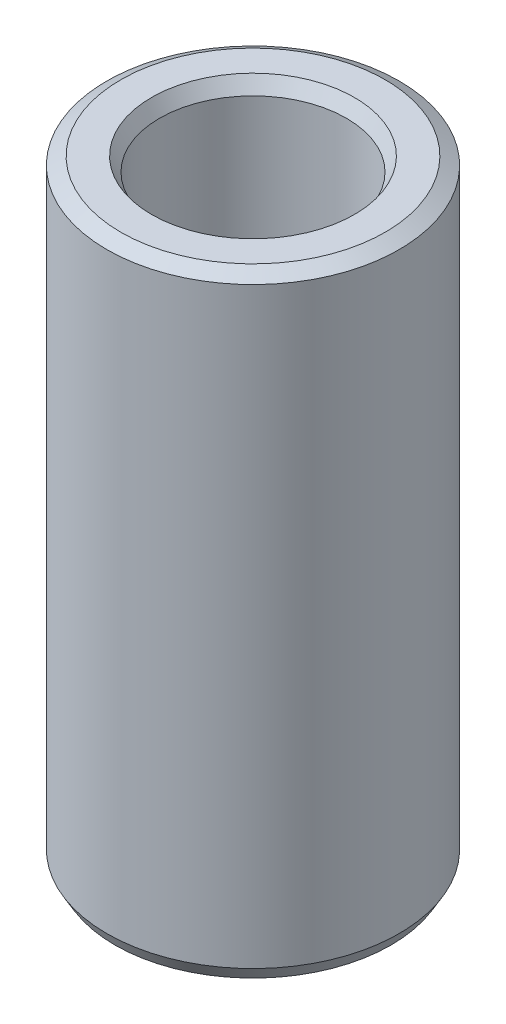
SolidWorks part; units mm, degrees
ref_plane "Front Plane" through (0, 0, 0) normal (0, 0, 1) x (1, 0, 0)
ref_plane "Top Plane" through (0, 0, 0) normal (0, 1, 0) x (1, 0, 0)
ref_plane "Right Plane" through (0, 0, 0) normal (1, 0, 0) x (0, 0, -1)
sketch "Sketch1" plane through (0, 0, 0) normal (0, 1, 0) x (1, 0, 0)
  circle A0 centre (0, 0) radius 22.5
  dimension "SLEEVE_OD" = 45
extrude "Boss-Extrude1" add sketch "Sketch1" along normal blind 94.6038
sketch "Sketch2" plane through (0, 0, 0) normal (0, 1, 0) x (1, 0, 0)
  circle A0 centre (0, 0) radius 14.3786
  dimension "BORE_D" = 28.7571
extrude "Cut-Extrude1" cut sketch "Sketch2" along normal through all
chamfer "Chamfer1" distance 1.2404 angle 60 4 edges at (0, 94.6038, 14.3786) (0, 0, 14.3786) (0, 0, 22.5) (0, 94.6038, 22.5) first distance on face at (0, 94.6038, 14.3786) first distance on face at (0, 0, 14.3786) first distance on face at (0, 94.6038, 22.5)
